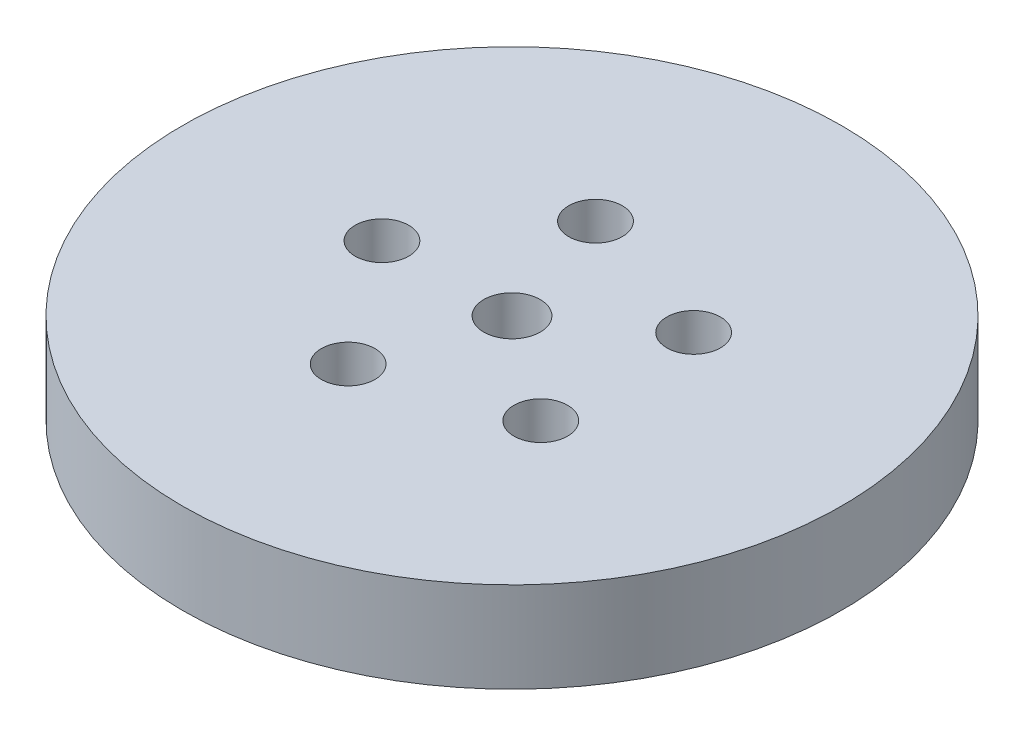
SolidWorks part; units mm, degrees
ref_plane "Front Plane" through (0, 0, 0) normal (0, 0, 1) x (1, 0, 0)
ref_plane "Top Plane" through (0, 0, 0) normal (0, 1, 0) x (1, 0, 0)
ref_plane "Right Plane" through (0, 0, 0) normal (1, 0, 0) x (0, 0, -1)
sketch "Sketch1" plane through (0, 0, 0) normal (0, 1, 0) x (1, 0, 0)
  circle A0 centre (0, 0) radius 87.5
  dimension "FLANGE_OD" = 175
extrude "Boss-Extrude1" add sketch "Sketch1" along normal blind 24
sketch "Sketch2" plane through (0, 0, 0) normal (0, 1, 0) x (1, 0, 0)
  circle A0 centre (0, 0) radius 7.5
  dimension "BORE_D" = 15
extrude "Cut-Extrude1" cut sketch "Sketch2" along normal through all
sketch "Sketch3" plane through (0, 24, 0) normal (0, 1, 0) x (1, 0, 0)
  circle A0 centre (0, 0) radius 34.5289 construction
  circle A1 centre (-34.5289, 0) radius 7.1207
  dimension "BOLT_D" = 14.2414
  dimension "BOLT_PCD" = 69.0579
extrude "Cut-Extrude2" cut sketch "Sketch3" against normal blind 22.3185
pattern_circular "CirPattern1" count 5 over 360 about axis through (0, 0, 0) along (0, 1, 0) of "Cut-Extrude2"
